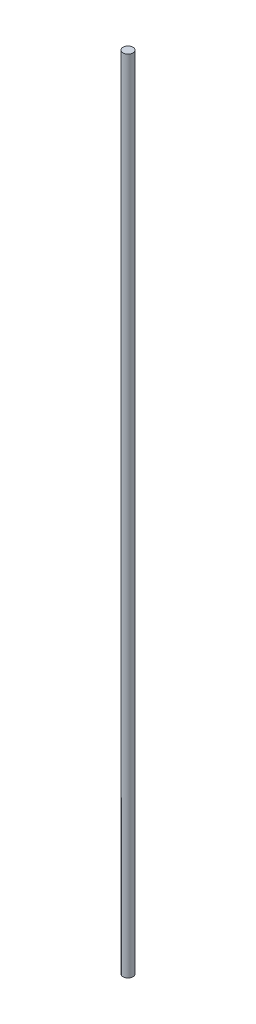
SolidWorks part; units mm, degrees
ref_plane "Front Plane" through (0, 0, 0) normal (0, 0, 1) x (1, 0, 0)
ref_plane "Top Plane" through (0, 0, 0) normal (0, 1, 0) x (1, 0, 0)
ref_plane "Right Plane" through (0, 0, 0) normal (1, 0, 0) x (0, 0, -1)
sketch "Sketch1" plane through (0, 0, 0) normal (0, 1, 0) x (1, 0, 0)
  circle A0 centre (0, 0) radius 5.08
extrude "Boss-Extrude1" add sketch "Sketch1" along normal blind 820.42
